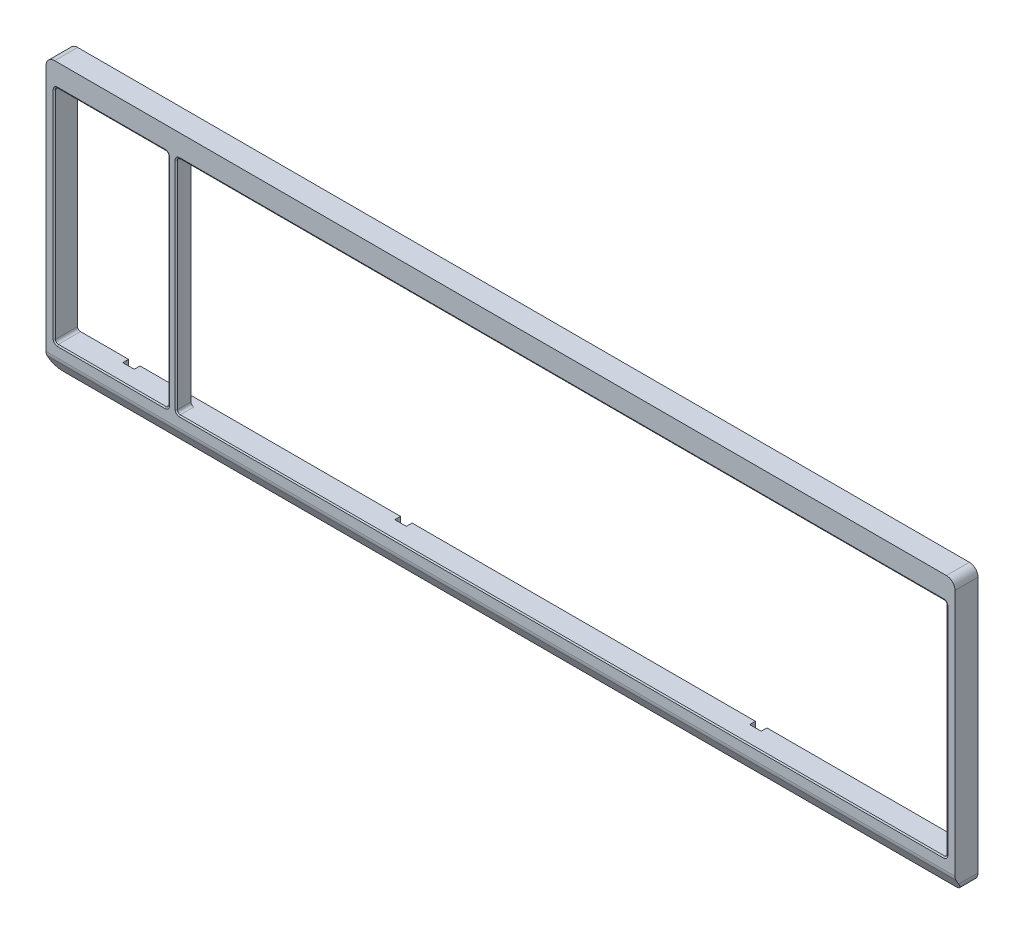
SolidWorks part; units mm, degrees
note: The reader was unsure of these and kept them because the rebuilt part matched: shared geometry of "Sketch3<3>".
ref_plane "Front Plane" through (0, 0, 0) normal (0, 0, 1) x (1, 0, 0)
ref_plane "Top Plane" through (0, 0, 0) normal (0, 1, 0) x (1, 0, 0)
ref_plane "Right Plane" through (0, 0, 0) normal (1, 0, 0) x (0, 0, -1)
sketch "Model" plane through (0, 0, 0) normal (0, 0, 1) x (1, 0, 0)
  line L0 (3.025, -2.525) -> (16.025, -2.525)
  line L1 (3.025, -16.525) -> (16.025, -16.525)
  line L2 (2.525, -3.025) -> (2.525, -16.025)
  line L3 (16.525, -3.025) -> (16.525, -16.025)
  line L4 (22.075, -2.525) -> (35.075, -2.525)
  line L5 (22.075, -16.525) -> (35.075, -16.525)
  line L6 (21.575, -3.025) -> (21.575, -16.025)
  line L7 (35.575, -3.025) -> (35.575, -16.025)
  line L8 (45.8875, -2.525) -> (58.8875, -2.525)
  line L9 (45.8875, -16.525) -> (58.8875, -16.525)
  line L10 (45.3875, -3.025) -> (45.3875, -16.025)
  line L11 (59.3875, -3.025) -> (59.3875, -16.025)
  line L12 (64.9375, -2.525) -> (77.9375, -2.525)
  line L13 (64.9375, -16.525) -> (77.9375, -16.525)
  line L14 (64.4375, -3.025) -> (64.4375, -16.025)
  line L15 (78.4375, -3.025) -> (78.4375, -16.025)
  line L16 (83.9875, -2.525) -> (96.9875, -2.525)
  line L17 (83.9875, -16.525) -> (96.9875, -16.525)
  line L18 (83.4875, -3.025) -> (83.4875, -16.025)
  line L19 (97.4875, -3.025) -> (97.4875, -16.025)
  line L20 (103.0375, -2.525) -> (116.0375, -2.525)
  line L21 (103.0375, -16.525) -> (116.0375, -16.525)
  line L22 (102.5375, -3.025) -> (102.5375, -16.025)
  line L23 (116.5375, -3.025) -> (116.5375, -16.025)
  line L24 (122.0875, -2.525) -> (135.0875, -2.525)
  line L25 (122.0875, -16.525) -> (135.0875, -16.525)
  line L26 (121.5875, -3.025) -> (121.5875, -16.025)
  line L27 (135.5875, -3.025) -> (135.5875, -16.025)
  line L28 (141.1375, -2.525) -> (154.1375, -2.525)
  line L29 (141.1375, -16.525) -> (154.1375, -16.525)
  line L30 (140.6375, -3.025) -> (140.6375, -16.025)
  line L31 (154.6375, -3.025) -> (154.6375, -16.025)
  line L32 (160.1875, -2.525) -> (173.1875, -2.525)
  line L33 (160.1875, -16.525) -> (173.1875, -16.525)
  line L34 (159.6875, -3.025) -> (159.6875, -16.025)
  line L35 (173.6875, -3.025) -> (173.6875, -16.025)
  line L36 (179.2375, -2.525) -> (192.2375, -2.525)
  line L37 (179.2375, -16.525) -> (192.2375, -16.525)
  line L38 (178.7375, -3.025) -> (178.7375, -16.025)
  line L39 (192.7375, -3.025) -> (192.7375, -16.025)
  line L40 (198.2875, -2.525) -> (211.2875, -2.525)
  line L41 (198.2875, -16.525) -> (211.2875, -16.525)
  line L42 (197.7875, -3.025) -> (197.7875, -16.025)
  line L43 (211.7875, -3.025) -> (211.7875, -16.025)
  line L44 (217.3375, -2.525) -> (230.3375, -2.525)
  line L45 (217.3375, -16.525) -> (230.3375, -16.525)
  line L46 (216.8375, -3.025) -> (216.8375, -16.025)
  line L47 (230.8375, -3.025) -> (230.8375, -16.025)
  line L48 (236.3875, -2.525) -> (249.3875, -2.525)
  line L49 (236.3875, -16.525) -> (249.3875, -16.525)
  line L50 (235.8875, -3.025) -> (235.8875, -16.025)
  line L51 (249.8875, -3.025) -> (249.8875, -16.025)
  line L52 (255.4375, -2.525) -> (268.4375, -2.525)
  line L53 (255.4375, -16.525) -> (268.4375, -16.525)
  line L54 (254.9375, -3.025) -> (254.9375, -16.025)
  line L55 (268.9375, -3.025) -> (268.9375, -16.025)
  line L56 (274.4875, -2.525) -> (287.4875, -2.525)
  line L57 (274.4875, -16.525) -> (287.4875, -16.525)
  line L58 (273.9875, -3.025) -> (273.9875, -16.025)
  line L59 (287.9875, -3.025) -> (287.9875, -16.025)
  line L60 (293.5375, -2.525) -> (306.5375, -2.525)
  line L61 (293.5375, -16.525) -> (306.5375, -16.525)
  line L62 (293.0375, -3.025) -> (293.0375, -16.025)
  line L63 (307.0375, -3.025) -> (307.0375, -16.025)
  line L64 (3.025, -21.575) -> (16.025, -21.575)
  line L65 (3.025, -35.575) -> (16.025, -35.575)
  line L66 (2.525, -22.075) -> (2.525, -35.075)
  line L67 (16.525, -22.075) -> (16.525, -35.075)
  line L68 (22.075, -21.575) -> (35.075, -21.575)
  line L69 (22.075, -35.575) -> (35.075, -35.575)
  line L70 (21.575, -22.075) -> (21.575, -35.075)
  line L71 (35.575, -22.075) -> (35.575, -35.075)
  line L72 (48.2687, -21.575) -> (61.2687, -21.575)
  line L73 (48.2687, -35.575) -> (61.2687, -35.575)
  line L74 (47.7687, -22.075) -> (47.7687, -35.075)
  line L75 (61.7687, -22.075) -> (61.7687, -35.075)
  line L76 (69.7, -21.575) -> (82.7, -21.575)
  line L77 (69.7, -35.575) -> (82.7, -35.575)
  line L78 (69.2, -22.075) -> (69.2, -35.075)
  line L79 (83.2, -22.075) -> (83.2, -35.075)
  line L80 (88.75, -21.575) -> (101.75, -21.575)
  line L81 (88.75, -35.575) -> (101.75, -35.575)
  line L82 (88.25, -22.075) -> (88.25, -35.075)
  line L83 (102.25, -22.075) -> (102.25, -35.075)
  line L84 (107.8, -21.575) -> (120.8, -21.575)
  line L85 (107.8, -35.575) -> (120.8, -35.575)
  line L86 (107.3, -22.075) -> (107.3, -35.075)
  line L87 (121.3, -22.075) -> (121.3, -35.075)
  line L88 (126.85, -21.575) -> (139.85, -21.575)
  line L89 (126.85, -35.575) -> (139.85, -35.575)
  line L90 (126.35, -22.075) -> (126.35, -35.075)
  line L91 (140.35, -22.075) -> (140.35, -35.075)
  line L92 (145.9, -21.575) -> (158.9, -21.575)
  line L93 (145.9, -35.575) -> (158.9, -35.575)
  line L94 (145.4, -22.075) -> (145.4, -35.075)
  line L95 (159.4, -22.075) -> (159.4, -35.075)
  line L96 (164.95, -21.575) -> (177.95, -21.575)
  line L97 (164.95, -35.575) -> (177.95, -35.575)
  line L98 (164.45, -22.075) -> (164.45, -35.075)
  line L99 (178.45, -22.075) -> (178.45, -35.075)
  line L100 (184, -21.575) -> (197, -21.575)
  line L101 (184, -35.575) -> (197, -35.575)
  line L102 (183.5, -22.075) -> (183.5, -35.075)
  line L103 (197.5, -22.075) -> (197.5, -35.075)
  line L104 (203.05, -21.575) -> (216.05, -21.575)
  line L105 (203.05, -35.575) -> (216.05, -35.575)
  line L106 (202.55, -22.075) -> (202.55, -35.075)
  line L107 (216.55, -22.075) -> (216.55, -35.075)
  line L108 (222.1, -21.575) -> (235.1, -21.575)
  line L109 (222.1, -35.575) -> (235.1, -35.575)
  line L110 (221.6, -22.075) -> (221.6, -35.075)
  line L111 (235.6, -22.075) -> (235.6, -35.075)
  line L112 (241.15, -21.575) -> (254.15, -21.575)
  line L113 (241.15, -35.575) -> (254.15, -35.575)
  line L114 (240.65, -22.075) -> (240.65, -35.075)
  line L115 (254.65, -22.075) -> (254.65, -35.075)
  line L116 (260.2, -21.575) -> (273.2, -21.575)
  line L117 (260.2, -35.575) -> (273.2, -35.575)
  line L118 (259.7, -22.075) -> (259.7, -35.075)
  line L119 (273.7, -22.075) -> (273.7, -35.075)
  line L120 (286.3938, -21.575) -> (299.3938, -21.575)
  line L121 (286.3938, -35.575) -> (299.3938, -35.575)
  line L122 (285.8938, -22.075) -> (285.8938, -35.075)
  line L123 (299.8938, -22.075) -> (299.8938, -35.075)
  line L124 (281.8938, -21.575) -> (282.3938, -21.575)
  line L125 (281.8938, -35.575) -> (282.3938, -35.575)
  line L126 (281.3938, -22.075) -> (281.3938, -35.075)
  line L127 (282.8938, -22.075) -> (282.8938, -35.075)
  line L128 (303.3938, -21.575) -> (303.8938, -21.575)
  line L129 (303.3938, -35.575) -> (303.8938, -35.575)
  line L130 (302.8938, -22.075) -> (302.8938, -35.075)
  line L131 (304.3938, -22.075) -> (304.3938, -35.075)
  line L132 (3.025, -40.625) -> (16.025, -40.625)
  line L133 (3.025, -54.625) -> (16.025, -54.625)
  line L134 (2.525, -41.125) -> (2.525, -54.125)
  line L135 (16.525, -41.125) -> (16.525, -54.125)
  line L136 (22.075, -40.625) -> (35.075, -40.625)
  line L137 (22.075, -54.625) -> (35.075, -54.625)
  line L138 (21.575, -41.125) -> (21.575, -54.125)
  line L139 (35.575, -41.125) -> (35.575, -54.125)
  line L140 (53.0312, -40.625) -> (66.0312, -40.625)
  line L141 (53.0312, -54.625) -> (66.0312, -54.625)
  line L142 (52.5312, -41.125) -> (52.5312, -54.125)
  line L143 (66.5312, -41.125) -> (66.5312, -54.125)
  line L144 (48.5312, -40.625) -> (49.0312, -40.625)
  line L145 (48.5312, -54.625) -> (49.0312, -54.625)
  line L146 (48.0312, -41.125) -> (48.0312, -54.125)
  line L147 (49.5312, -41.125) -> (49.5312, -54.125)
  line L148 (70.0312, -40.625) -> (70.5312, -40.625)
  line L149 (70.0312, -54.625) -> (70.5312, -54.625)
  line L150 (69.5312, -41.125) -> (69.5312, -54.125)
  line L151 (71.0312, -41.125) -> (71.0312, -54.125)
  line L152 (79.225, -40.625) -> (92.225, -40.625)
  line L153 (79.225, -54.625) -> (92.225, -54.625)
  line L154 (78.725, -41.125) -> (78.725, -54.125)
  line L155 (92.725, -41.125) -> (92.725, -54.125)
  line L156 (98.275, -40.625) -> (111.275, -40.625)
  line L157 (98.275, -54.625) -> (111.275, -54.625)
  line L158 (97.775, -41.125) -> (97.775, -54.125)
  line L159 (111.775, -41.125) -> (111.775, -54.125)
  line L160 (117.325, -40.625) -> (130.325, -40.625)
  line L161 (117.325, -54.625) -> (130.325, -54.625)
  line L162 (116.825, -41.125) -> (116.825, -54.125)
  line L163 (130.825, -41.125) -> (130.825, -54.125)
  line L164 (136.375, -40.625) -> (149.375, -40.625)
  line L165 (136.375, -54.625) -> (149.375, -54.625)
  line L166 (135.875, -41.125) -> (135.875, -54.125)
  line L167 (149.875, -41.125) -> (149.875, -54.125)
  line L168 (155.425, -40.625) -> (168.425, -40.625)
  line L169 (155.425, -54.625) -> (168.425, -54.625)
  line L170 (154.925, -41.125) -> (154.925, -54.125)
  line L171 (168.925, -41.125) -> (168.925, -54.125)
  line L172 (174.475, -40.625) -> (187.475, -40.625)
  line L173 (174.475, -54.625) -> (187.475, -54.625)
  line L174 (173.975, -41.125) -> (173.975, -54.125)
  line L175 (187.975, -41.125) -> (187.975, -54.125)
  line L176 (193.525, -40.625) -> (206.525, -40.625)
  line L177 (193.525, -54.625) -> (206.525, -54.625)
  line L178 (193.025, -41.125) -> (193.025, -54.125)
  line L179 (207.025, -41.125) -> (207.025, -54.125)
  line L180 (212.575, -40.625) -> (225.575, -40.625)
  line L181 (212.575, -54.625) -> (225.575, -54.625)
  line L182 (212.075, -41.125) -> (212.075, -54.125)
  line L183 (226.075, -41.125) -> (226.075, -54.125)
  line L184 (231.625, -40.625) -> (244.625, -40.625)
  line L185 (231.625, -54.625) -> (244.625, -54.625)
  line L186 (231.125, -41.125) -> (231.125, -54.125)
  line L187 (245.125, -41.125) -> (245.125, -54.125)
  line L188 (250.675, -40.625) -> (263.675, -40.625)
  line L189 (250.675, -54.625) -> (263.675, -54.625)
  line L190 (250.175, -41.125) -> (250.175, -54.125)
  line L191 (264.175, -41.125) -> (264.175, -54.125)
  line L192 (269.725, -40.625) -> (282.725, -40.625)
  line L193 (269.725, -54.625) -> (282.725, -54.625)
  line L194 (269.225, -41.125) -> (269.225, -54.125)
  line L195 (283.225, -41.125) -> (283.225, -54.125)
  line L196 (291.1562, -40.625) -> (304.1562, -40.625)
  line L197 (291.1562, -54.625) -> (304.1562, -54.625)
  line L198 (290.6562, -41.125) -> (290.6562, -54.125)
  line L199 (304.6562, -41.125) -> (304.6562, -54.125)
  line L200 (3.025, -59.675) -> (16.025, -59.675)
  line L201 (3.025, -73.675) -> (16.025, -73.675)
  line L202 (2.525, -60.175) -> (2.525, -73.175)
  line L203 (16.525, -60.175) -> (16.525, -73.175)
  line L204 (22.075, -59.675) -> (35.075, -59.675)
  line L205 (22.075, -73.675) -> (35.075, -73.675)
  line L206 (21.575, -60.175) -> (21.575, -73.175)
  line L207 (35.575, -60.175) -> (35.575, -73.175)
  line L208 (48.2687, -59.675) -> (61.2687, -59.675)
  line L209 (48.2687, -73.675) -> (61.2687, -73.675)
  line L210 (47.7687, -60.175) -> (47.7687, -73.175)
  line L211 (61.7687, -60.175) -> (61.7687, -73.175)
  line L212 (69.7, -59.675) -> (82.7, -59.675)
  line L213 (69.7, -73.675) -> (82.7, -73.675)
  line L214 (69.2, -60.175) -> (69.2, -73.175)
  line L215 (83.2, -60.175) -> (83.2, -73.175)
  line L216 (93.5125, -59.675) -> (106.5125, -59.675)
  line L217 (93.5125, -73.675) -> (106.5125, -73.675)
  line L218 (93.0125, -60.175) -> (93.0125, -73.175)
  line L219 (107.0125, -60.175) -> (107.0125, -73.175)
  line L220 (89.0125, -59.675) -> (89.5125, -59.675)
  line L221 (89.0125, -73.675) -> (89.5125, -73.675)
  line L222 (88.5125, -60.175) -> (88.5125, -73.175)
  line L223 (90.0125, -60.175) -> (90.0125, -73.175)
  line L224 (110.5125, -59.675) -> (111.0125, -59.675)
  line L225 (110.5125, -73.675) -> (111.0125, -73.675)
  line L226 (110.0125, -60.175) -> (110.0125, -73.175)
  line L227 (111.5125, -60.175) -> (111.5125, -73.175)
  line L228 (167.3313, -59.675) -> (180.3313, -59.675)
  line L229 (167.3313, -73.675) -> (180.3313, -73.675)
  line L230 (166.8313, -60.175) -> (166.8313, -73.175)
  line L231 (180.8313, -60.175) -> (180.8313, -73.175)
  line L232 (120.8312, -60.675) -> (126.8313, -60.675)
  line L233 (120.8312, -75.675) -> (126.8313, -75.675)
  line L234 (120.3312, -61.175) -> (120.3312, -75.175)
  line L235 (127.3313, -61.175) -> (127.3313, -75.175)
  line L236 (220.8313, -60.675) -> (226.8313, -60.675)
  line L237 (220.8313, -75.675) -> (226.8313, -75.675)
  line L238 (220.3313, -61.175) -> (220.3313, -75.175)
  line L239 (227.3313, -61.175) -> (227.3313, -75.175)
  line L240 (241.15, -59.675) -> (254.15, -59.675)
  line L241 (241.15, -73.675) -> (254.15, -73.675)
  line L242 (240.65, -60.175) -> (240.65, -73.175)
  line L243 (254.65, -60.175) -> (254.65, -73.175)
  line L244 (236.65, -59.675) -> (237.15, -59.675)
  line L245 (236.65, -73.675) -> (237.15, -73.675)
  line L246 (236.15, -60.175) -> (236.15, -73.175)
  line L247 (237.65, -60.175) -> (237.65, -73.175)
  line L248 (258.15, -59.675) -> (258.65, -59.675)
  line L249 (258.15, -73.675) -> (258.65, -73.675)
  line L250 (257.65, -60.175) -> (257.65, -73.175)
  line L251 (259.15, -60.175) -> (259.15, -73.175)
  line L252 (264.9625, -59.675) -> (277.9625, -59.675)
  line L253 (264.9625, -73.675) -> (277.9625, -73.675)
  line L254 (264.4625, -60.175) -> (264.4625, -73.175)
  line L255 (278.4625, -60.175) -> (278.4625, -73.175)
  line L256 (288.775, -59.675) -> (301.775, -59.675)
  line L257 (288.775, -73.675) -> (301.775, -73.675)
  line L258 (288.275, -60.175) -> (288.275, -73.175)
  line L259 (302.275, -60.175) -> (302.275, -73.175)
  line L260 (284.275, -59.675) -> (284.775, -59.675)
  line L261 (284.275, -73.675) -> (284.775, -73.675)
  line L262 (283.775, -60.175) -> (283.775, -73.175)
  line L263 (285.275, -60.175) -> (285.275, -73.175)
  line L264 (305.775, -59.675) -> (306.275, -59.675)
  line L265 (305.775, -73.675) -> (306.275, -73.675)
  line L266 (305.275, -60.175) -> (305.275, -73.175)
  line L267 (306.775, -60.175) -> (306.775, -73.175)
  line L268 (0, -76.2) -> (309.5625, -76.2)
  line L269 (0, 0) -> (309.5625, 0)
  line L270 (0, -76.2) -> (0, 0)
  line L271 (309.5625, -76.2) -> (309.5625, 0)
  arc A0 (3.025, -2.525) -> (2.525, -3.025) centre (3.025, -3.025) ccw
  arc A1 (16.525, -3.025) -> (16.025, -2.525) centre (16.025, -3.025) ccw
  arc A2 (2.525, -16.025) -> (3.025, -16.525) centre (3.025, -16.025) ccw
  arc A3 (16.025, -16.525) -> (16.525, -16.025) centre (16.025, -16.025) ccw
  arc A4 (22.075, -2.525) -> (21.575, -3.025) centre (22.075, -3.025) ccw
  arc A5 (35.575, -3.025) -> (35.075, -2.525) centre (35.075, -3.025) ccw
  arc A6 (21.575, -16.025) -> (22.075, -16.525) centre (22.075, -16.025) ccw
  arc A7 (35.075, -16.525) -> (35.575, -16.025) centre (35.075, -16.025) ccw
  arc A8 (45.8875, -2.525) -> (45.3875, -3.025) centre (45.8875, -3.025) ccw
  arc A9 (59.3875, -3.025) -> (58.8875, -2.525) centre (58.8875, -3.025) ccw
  arc A10 (45.3875, -16.025) -> (45.8875, -16.525) centre (45.8875, -16.025) ccw
  arc A11 (58.8875, -16.525) -> (59.3875, -16.025) centre (58.8875, -16.025) ccw
  arc A12 (64.9375, -2.525) -> (64.4375, -3.025) centre (64.9375, -3.025) ccw
  arc A13 (78.4375, -3.025) -> (77.9375, -2.525) centre (77.9375, -3.025) ccw
  arc A14 (64.4375, -16.025) -> (64.9375, -16.525) centre (64.9375, -16.025) ccw
  arc A15 (77.9375, -16.525) -> (78.4375, -16.025) centre (77.9375, -16.025) ccw
  arc A16 (83.9875, -2.525) -> (83.4875, -3.025) centre (83.9875, -3.025) ccw
  arc A17 (97.4875, -3.025) -> (96.9875, -2.525) centre (96.9875, -3.025) ccw
  arc A18 (83.4875, -16.025) -> (83.9875, -16.525) centre (83.9875, -16.025) ccw
  arc A19 (96.9875, -16.525) -> (97.4875, -16.025) centre (96.9875, -16.025) ccw
  arc A20 (103.0375, -2.525) -> (102.5375, -3.025) centre (103.0375, -3.025) ccw
  arc A21 (116.5375, -3.025) -> (116.0375, -2.525) centre (116.0375, -3.025) ccw
  arc A22 (102.5375, -16.025) -> (103.0375, -16.525) centre (103.0375, -16.025) ccw
  arc A23 (116.0375, -16.525) -> (116.5375, -16.025) centre (116.0375, -16.025) ccw
  arc A24 (122.0875, -2.525) -> (121.5875, -3.025) centre (122.0875, -3.025) ccw
  arc A25 (135.5875, -3.025) -> (135.0875, -2.525) centre (135.0875, -3.025) ccw
  arc A26 (121.5875, -16.025) -> (122.0875, -16.525) centre (122.0875, -16.025) ccw
  arc A27 (135.0875, -16.525) -> (135.5875, -16.025) centre (135.0875, -16.025) ccw
  arc A28 (141.1375, -2.525) -> (140.6375, -3.025) centre (141.1375, -3.025) ccw
  arc A29 (154.6375, -3.025) -> (154.1375, -2.525) centre (154.1375, -3.025) ccw
  arc A30 (140.6375, -16.025) -> (141.1375, -16.525) centre (141.1375, -16.025) ccw
  arc A31 (154.1375, -16.525) -> (154.6375, -16.025) centre (154.1375, -16.025) ccw
  arc A32 (160.1875, -2.525) -> (159.6875, -3.025) centre (160.1875, -3.025) ccw
  arc A33 (173.6875, -3.025) -> (173.1875, -2.525) centre (173.1875, -3.025) ccw
  arc A34 (159.6875, -16.025) -> (160.1875, -16.525) centre (160.1875, -16.025) ccw
  arc A35 (173.1875, -16.525) -> (173.6875, -16.025) centre (173.1875, -16.025) ccw
  arc A36 (179.2375, -2.525) -> (178.7375, -3.025) centre (179.2375, -3.025) ccw
  arc A37 (192.7375, -3.025) -> (192.2375, -2.525) centre (192.2375, -3.025) ccw
  arc A38 (178.7375, -16.025) -> (179.2375, -16.525) centre (179.2375, -16.025) ccw
  arc A39 (192.2375, -16.525) -> (192.7375, -16.025) centre (192.2375, -16.025) ccw
  arc A40 (198.2875, -2.525) -> (197.7875, -3.025) centre (198.2875, -3.025) ccw
  arc A41 (211.7875, -3.025) -> (211.2875, -2.525) centre (211.2875, -3.025) ccw
  arc A42 (197.7875, -16.025) -> (198.2875, -16.525) centre (198.2875, -16.025) ccw
  arc A43 (211.2875, -16.525) -> (211.7875, -16.025) centre (211.2875, -16.025) ccw
  arc A44 (217.3375, -2.525) -> (216.8375, -3.025) centre (217.3375, -3.025) ccw
  arc A45 (230.8375, -3.025) -> (230.3375, -2.525) centre (230.3375, -3.025) ccw
  arc A46 (216.8375, -16.025) -> (217.3375, -16.525) centre (217.3375, -16.025) ccw
  arc A47 (230.3375, -16.525) -> (230.8375, -16.025) centre (230.3375, -16.025) ccw
  arc A48 (236.3875, -2.525) -> (235.8875, -3.025) centre (236.3875, -3.025) ccw
  arc A49 (249.8875, -3.025) -> (249.3875, -2.525) centre (249.3875, -3.025) ccw
  arc A50 (235.8875, -16.025) -> (236.3875, -16.525) centre (236.3875, -16.025) ccw
  arc A51 (249.3875, -16.525) -> (249.8875, -16.025) centre (249.3875, -16.025) ccw
  arc A52 (255.4375, -2.525) -> (254.9375, -3.025) centre (255.4375, -3.025) ccw
  arc A53 (268.9375, -3.025) -> (268.4375, -2.525) centre (268.4375, -3.025) ccw
  arc A54 (254.9375, -16.025) -> (255.4375, -16.525) centre (255.4375, -16.025) ccw
  arc A55 (268.4375, -16.525) -> (268.9375, -16.025) centre (268.4375, -16.025) ccw
  arc A56 (274.4875, -2.525) -> (273.9875, -3.025) centre (274.4875, -3.025) ccw
  arc A57 (287.9875, -3.025) -> (287.4875, -2.525) centre (287.4875, -3.025) ccw
  arc A58 (273.9875, -16.025) -> (274.4875, -16.525) centre (274.4875, -16.025) ccw
  arc A59 (287.4875, -16.525) -> (287.9875, -16.025) centre (287.4875, -16.025) ccw
  arc A60 (293.5375, -2.525) -> (293.0375, -3.025) centre (293.5375, -3.025) ccw
  arc A61 (307.0375, -3.025) -> (306.5375, -2.525) centre (306.5375, -3.025) ccw
  arc A62 (293.0375, -16.025) -> (293.5375, -16.525) centre (293.5375, -16.025) ccw
  arc A63 (306.5375, -16.525) -> (307.0375, -16.025) centre (306.5375, -16.025) ccw
  arc A64 (3.025, -21.575) -> (2.525, -22.075) centre (3.025, -22.075) ccw
  arc A65 (16.525, -22.075) -> (16.025, -21.575) centre (16.025, -22.075) ccw
  arc A66 (2.525, -35.075) -> (3.025, -35.575) centre (3.025, -35.075) ccw
  arc A67 (16.025, -35.575) -> (16.525, -35.075) centre (16.025, -35.075) ccw
  arc A68 (22.075, -21.575) -> (21.575, -22.075) centre (22.075, -22.075) ccw
  arc A69 (35.575, -22.075) -> (35.075, -21.575) centre (35.075, -22.075) ccw
  arc A70 (21.575, -35.075) -> (22.075, -35.575) centre (22.075, -35.075) ccw
  arc A71 (35.075, -35.575) -> (35.575, -35.075) centre (35.075, -35.075) ccw
  arc A72 (48.2687, -21.575) -> (47.7687, -22.075) centre (48.2687, -22.075) ccw
  arc A73 (61.7687, -22.075) -> (61.2687, -21.575) centre (61.2687, -22.075) ccw
  arc A74 (47.7687, -35.075) -> (48.2687, -35.575) centre (48.2687, -35.075) ccw
  arc A75 (61.2687, -35.575) -> (61.7687, -35.075) centre (61.2687, -35.075) ccw
  arc A76 (69.7, -21.575) -> (69.2, -22.075) centre (69.7, -22.075) ccw
  arc A77 (83.2, -22.075) -> (82.7, -21.575) centre (82.7, -22.075) ccw
  arc A78 (69.2, -35.075) -> (69.7, -35.575) centre (69.7, -35.075) ccw
  arc A79 (82.7, -35.575) -> (83.2, -35.075) centre (82.7, -35.075) ccw
  arc A80 (88.75, -21.575) -> (88.25, -22.075) centre (88.75, -22.075) ccw
  arc A81 (102.25, -22.075) -> (101.75, -21.575) centre (101.75, -22.075) ccw
  arc A82 (88.25, -35.075) -> (88.75, -35.575) centre (88.75, -35.075) ccw
  arc A83 (101.75, -35.575) -> (102.25, -35.075) centre (101.75, -35.075) ccw
  arc A84 (107.8, -21.575) -> (107.3, -22.075) centre (107.8, -22.075) ccw
  arc A85 (121.3, -22.075) -> (120.8, -21.575) centre (120.8, -22.075) ccw
  arc A86 (107.3, -35.075) -> (107.8, -35.575) centre (107.8, -35.075) ccw
  arc A87 (120.8, -35.575) -> (121.3, -35.075) centre (120.8, -35.075) ccw
  arc A88 (126.85, -21.575) -> (126.35, -22.075) centre (126.85, -22.075) ccw
  arc A89 (140.35, -22.075) -> (139.85, -21.575) centre (139.85, -22.075) ccw
  arc A90 (126.35, -35.075) -> (126.85, -35.575) centre (126.85, -35.075) ccw
  arc A91 (139.85, -35.575) -> (140.35, -35.075) centre (139.85, -35.075) ccw
  arc A92 (145.9, -21.575) -> (145.4, -22.075) centre (145.9, -22.075) ccw
  arc A93 (159.4, -22.075) -> (158.9, -21.575) centre (158.9, -22.075) ccw
  arc A94 (145.4, -35.075) -> (145.9, -35.575) centre (145.9, -35.075) ccw
  arc A95 (158.9, -35.575) -> (159.4, -35.075) centre (158.9, -35.075) ccw
  arc A96 (164.95, -21.575) -> (164.45, -22.075) centre (164.95, -22.075) ccw
  arc A97 (178.45, -22.075) -> (177.95, -21.575) centre (177.95, -22.075) ccw
  arc A98 (164.45, -35.075) -> (164.95, -35.575) centre (164.95, -35.075) ccw
  arc A99 (177.95, -35.575) -> (178.45, -35.075) centre (177.95, -35.075) ccw
  arc A100 (184, -21.575) -> (183.5, -22.075) centre (184, -22.075) ccw
  arc A101 (197.5, -22.075) -> (197, -21.575) centre (197, -22.075) ccw
  arc A102 (183.5, -35.075) -> (184, -35.575) centre (184, -35.075) ccw
  arc A103 (197, -35.575) -> (197.5, -35.075) centre (197, -35.075) ccw
  arc A104 (203.05, -21.575) -> (202.55, -22.075) centre (203.05, -22.075) ccw
  arc A105 (216.55, -22.075) -> (216.05, -21.575) centre (216.05, -22.075) ccw
  arc A106 (202.55, -35.075) -> (203.05, -35.575) centre (203.05, -35.075) ccw
  arc A107 (216.05, -35.575) -> (216.55, -35.075) centre (216.05, -35.075) ccw
  arc A108 (222.1, -21.575) -> (221.6, -22.075) centre (222.1, -22.075) ccw
  arc A109 (235.6, -22.075) -> (235.1, -21.575) centre (235.1, -22.075) ccw
  arc A110 (221.6, -35.075) -> (222.1, -35.575) centre (222.1, -35.075) ccw
  arc A111 (235.1, -35.575) -> (235.6, -35.075) centre (235.1, -35.075) ccw
  arc A112 (241.15, -21.575) -> (240.65, -22.075) centre (241.15, -22.075) ccw
  arc A113 (254.65, -22.075) -> (254.15, -21.575) centre (254.15, -22.075) ccw
  arc A114 (240.65, -35.075) -> (241.15, -35.575) centre (241.15, -35.075) ccw
  arc A115 (254.15, -35.575) -> (254.65, -35.075) centre (254.15, -35.075) ccw
  arc A116 (260.2, -21.575) -> (259.7, -22.075) centre (260.2, -22.075) ccw
  arc A117 (273.7, -22.075) -> (273.2, -21.575) centre (273.2, -22.075) ccw
  arc A118 (259.7, -35.075) -> (260.2, -35.575) centre (260.2, -35.075) ccw
  arc A119 (273.2, -35.575) -> (273.7, -35.075) centre (273.2, -35.075) ccw
  arc A120 (286.3938, -21.575) -> (285.8938, -22.075) centre (286.3938, -22.075) ccw
  arc A121 (299.8938, -22.075) -> (299.3938, -21.575) centre (299.3938, -22.075) ccw
  arc A122 (285.8938, -35.075) -> (286.3938, -35.575) centre (286.3938, -35.075) ccw
  arc A123 (299.3938, -35.575) -> (299.8938, -35.075) centre (299.3938, -35.075) ccw
  arc A124 (281.8938, -21.575) -> (281.3938, -22.075) centre (281.8938, -22.075) ccw
  arc A125 (282.8938, -22.075) -> (282.3938, -21.575) centre (282.3938, -22.075) ccw
  arc A126 (281.3938, -35.075) -> (281.8938, -35.575) centre (281.8938, -35.075) ccw
  arc A127 (282.3938, -35.575) -> (282.8938, -35.075) centre (282.3938, -35.075) ccw
  arc A128 (303.3938, -21.575) -> (302.8938, -22.075) centre (303.3938, -22.075) ccw
  arc A129 (304.3938, -22.075) -> (303.8938, -21.575) centre (303.8938, -22.075) ccw
  arc A130 (302.8938, -35.075) -> (303.3938, -35.575) centre (303.3938, -35.075) ccw
  arc A131 (303.8938, -35.575) -> (304.3938, -35.075) centre (303.8938, -35.075) ccw
  arc A132 (3.025, -40.625) -> (2.525, -41.125) centre (3.025, -41.125) ccw
  arc A133 (16.525, -41.125) -> (16.025, -40.625) centre (16.025, -41.125) ccw
  arc A134 (2.525, -54.125) -> (3.025, -54.625) centre (3.025, -54.125) ccw
  arc A135 (16.025, -54.625) -> (16.525, -54.125) centre (16.025, -54.125) ccw
  arc A136 (22.075, -40.625) -> (21.575, -41.125) centre (22.075, -41.125) ccw
  arc A137 (35.575, -41.125) -> (35.075, -40.625) centre (35.075, -41.125) ccw
  arc A138 (21.575, -54.125) -> (22.075, -54.625) centre (22.075, -54.125) ccw
  arc A139 (35.075, -54.625) -> (35.575, -54.125) centre (35.075, -54.125) ccw
  arc A140 (53.0312, -40.625) -> (52.5312, -41.125) centre (53.0312, -41.125) ccw
  arc A141 (66.5312, -41.125) -> (66.0312, -40.625) centre (66.0312, -41.125) ccw
  arc A142 (52.5312, -54.125) -> (53.0312, -54.625) centre (53.0312, -54.125) ccw
  arc A143 (66.0312, -54.625) -> (66.5312, -54.125) centre (66.0312, -54.125) ccw
  arc A144 (48.5312, -40.625) -> (48.0312, -41.125) centre (48.5312, -41.125) ccw
  arc A145 (49.5312, -41.125) -> (49.0312, -40.625) centre (49.0312, -41.125) ccw
  arc A146 (48.0312, -54.125) -> (48.5312, -54.625) centre (48.5312, -54.125) ccw
  arc A147 (49.0312, -54.625) -> (49.5312, -54.125) centre (49.0312, -54.125) ccw
  arc A148 (70.0312, -40.625) -> (69.5312, -41.125) centre (70.0312, -41.125) ccw
  arc A149 (71.0312, -41.125) -> (70.5312, -40.625) centre (70.5312, -41.125) ccw
  arc A150 (69.5312, -54.125) -> (70.0312, -54.625) centre (70.0312, -54.125) ccw
  arc A151 (70.5312, -54.625) -> (71.0312, -54.125) centre (70.5312, -54.125) ccw
  arc A152 (79.225, -40.625) -> (78.725, -41.125) centre (79.225, -41.125) ccw
  arc A153 (92.725, -41.125) -> (92.225, -40.625) centre (92.225, -41.125) ccw
  arc A154 (78.725, -54.125) -> (79.225, -54.625) centre (79.225, -54.125) ccw
  arc A155 (92.225, -54.625) -> (92.725, -54.125) centre (92.225, -54.125) ccw
  arc A156 (98.275, -40.625) -> (97.775, -41.125) centre (98.275, -41.125) ccw
  arc A157 (111.775, -41.125) -> (111.275, -40.625) centre (111.275, -41.125) ccw
  arc A158 (97.775, -54.125) -> (98.275, -54.625) centre (98.275, -54.125) ccw
  arc A159 (111.275, -54.625) -> (111.775, -54.125) centre (111.275, -54.125) ccw
  arc A160 (117.325, -40.625) -> (116.825, -41.125) centre (117.325, -41.125) ccw
  arc A161 (130.825, -41.125) -> (130.325, -40.625) centre (130.325, -41.125) ccw
  arc A162 (116.825, -54.125) -> (117.325, -54.625) centre (117.325, -54.125) ccw
  arc A163 (130.325, -54.625) -> (130.825, -54.125) centre (130.325, -54.125) ccw
  arc A164 (136.375, -40.625) -> (135.875, -41.125) centre (136.375, -41.125) ccw
  arc A165 (149.875, -41.125) -> (149.375, -40.625) centre (149.375, -41.125) ccw
  arc A166 (135.875, -54.125) -> (136.375, -54.625) centre (136.375, -54.125) ccw
  arc A167 (149.375, -54.625) -> (149.875, -54.125) centre (149.375, -54.125) ccw
  arc A168 (155.425, -40.625) -> (154.925, -41.125) centre (155.425, -41.125) ccw
  arc A169 (168.925, -41.125) -> (168.425, -40.625) centre (168.425, -41.125) ccw
  arc A170 (154.925, -54.125) -> (155.425, -54.625) centre (155.425, -54.125) ccw
  arc A171 (168.425, -54.625) -> (168.925, -54.125) centre (168.425, -54.125) ccw
  arc A172 (174.475, -40.625) -> (173.975, -41.125) centre (174.475, -41.125) ccw
  arc A173 (187.975, -41.125) -> (187.475, -40.625) centre (187.475, -41.125) ccw
  arc A174 (173.975, -54.125) -> (174.475, -54.625) centre (174.475, -54.125) ccw
  arc A175 (187.475, -54.625) -> (187.975, -54.125) centre (187.475, -54.125) ccw
  arc A176 (193.525, -40.625) -> (193.025, -41.125) centre (193.525, -41.125) ccw
  arc A177 (207.025, -41.125) -> (206.525, -40.625) centre (206.525, -41.125) ccw
  arc A178 (193.025, -54.125) -> (193.525, -54.625) centre (193.525, -54.125) ccw
  arc A179 (206.525, -54.625) -> (207.025, -54.125) centre (206.525, -54.125) ccw
  arc A180 (212.575, -40.625) -> (212.075, -41.125) centre (212.575, -41.125) ccw
  arc A181 (226.075, -41.125) -> (225.575, -40.625) centre (225.575, -41.125) ccw
  arc A182 (212.075, -54.125) -> (212.575, -54.625) centre (212.575, -54.125) ccw
  arc A183 (225.575, -54.625) -> (226.075, -54.125) centre (225.575, -54.125) ccw
  arc A184 (231.625, -40.625) -> (231.125, -41.125) centre (231.625, -41.125) ccw
  arc A185 (245.125, -41.125) -> (244.625, -40.625) centre (244.625, -41.125) ccw
  arc A186 (231.125, -54.125) -> (231.625, -54.625) centre (231.625, -54.125) ccw
  arc A187 (244.625, -54.625) -> (245.125, -54.125) centre (244.625, -54.125) ccw
  arc A188 (250.675, -40.625) -> (250.175, -41.125) centre (250.675, -41.125) ccw
  arc A189 (264.175, -41.125) -> (263.675, -40.625) centre (263.675, -41.125) ccw
  arc A190 (250.175, -54.125) -> (250.675, -54.625) centre (250.675, -54.125) ccw
  arc A191 (263.675, -54.625) -> (264.175, -54.125) centre (263.675, -54.125) ccw
  arc A192 (269.725, -40.625) -> (269.225, -41.125) centre (269.725, -41.125) ccw
  arc A193 (283.225, -41.125) -> (282.725, -40.625) centre (282.725, -41.125) ccw
  arc A194 (269.225, -54.125) -> (269.725, -54.625) centre (269.725, -54.125) ccw
  arc A195 (282.725, -54.625) -> (283.225, -54.125) centre (282.725, -54.125) ccw
  arc A196 (291.1562, -40.625) -> (290.6562, -41.125) centre (291.1562, -41.125) ccw
  arc A197 (304.6562, -41.125) -> (304.1562, -40.625) centre (304.1562, -41.125) ccw
  arc A198 (290.6562, -54.125) -> (291.1562, -54.625) centre (291.1562, -54.125) ccw
  arc A199 (304.1562, -54.625) -> (304.6562, -54.125) centre (304.1562, -54.125) ccw
  arc A200 (3.025, -59.675) -> (2.525, -60.175) centre (3.025, -60.175) ccw
  arc A201 (16.525, -60.175) -> (16.025, -59.675) centre (16.025, -60.175) ccw
  arc A202 (2.525, -73.175) -> (3.025, -73.675) centre (3.025, -73.175) ccw
  arc A203 (16.025, -73.675) -> (16.525, -73.175) centre (16.025, -73.175) ccw
  arc A204 (22.075, -59.675) -> (21.575, -60.175) centre (22.075, -60.175) ccw
  arc A205 (35.575, -60.175) -> (35.075, -59.675) centre (35.075, -60.175) ccw
  arc A206 (21.575, -73.175) -> (22.075, -73.675) centre (22.075, -73.175) ccw
  arc A207 (35.075, -73.675) -> (35.575, -73.175) centre (35.075, -73.175) ccw
  arc A208 (48.2687, -59.675) -> (47.7687, -60.175) centre (48.2687, -60.175) ccw
  arc A209 (61.7687, -60.175) -> (61.2687, -59.675) centre (61.2687, -60.175) ccw
  arc A210 (47.7687, -73.175) -> (48.2687, -73.675) centre (48.2687, -73.175) ccw
  arc A211 (61.2687, -73.675) -> (61.7687, -73.175) centre (61.2687, -73.175) ccw
  arc A212 (69.7, -59.675) -> (69.2, -60.175) centre (69.7, -60.175) ccw
  arc A213 (83.2, -60.175) -> (82.7, -59.675) centre (82.7, -60.175) ccw
  arc A214 (69.2, -73.175) -> (69.7, -73.675) centre (69.7, -73.175) ccw
  arc A215 (82.7, -73.675) -> (83.2, -73.175) centre (82.7, -73.175) ccw
  arc A216 (93.5125, -59.675) -> (93.0125, -60.175) centre (93.5125, -60.175) ccw
  arc A217 (107.0125, -60.175) -> (106.5125, -59.675) centre (106.5125, -60.175) ccw
  arc A218 (93.0125, -73.175) -> (93.5125, -73.675) centre (93.5125, -73.175) ccw
  arc A219 (106.5125, -73.675) -> (107.0125, -73.175) centre (106.5125, -73.175) ccw
  arc A220 (89.0125, -59.675) -> (88.5125, -60.175) centre (89.0125, -60.175) ccw
  arc A221 (90.0125, -60.175) -> (89.5125, -59.675) centre (89.5125, -60.175) ccw
  arc A222 (88.5125, -73.175) -> (89.0125, -73.675) centre (89.0125, -73.175) ccw
  arc A223 (89.5125, -73.675) -> (90.0125, -73.175) centre (89.5125, -73.175) ccw
  arc A224 (110.5125, -59.675) -> (110.0125, -60.175) centre (110.5125, -60.175) ccw
  arc A225 (111.5125, -60.175) -> (111.0125, -59.675) centre (111.0125, -60.175) ccw
  arc A226 (110.0125, -73.175) -> (110.5125, -73.675) centre (110.5125, -73.175) ccw
  arc A227 (111.0125, -73.675) -> (111.5125, -73.175) centre (111.0125, -73.175) ccw
  arc A228 (167.3313, -59.675) -> (166.8313, -60.175) centre (167.3313, -60.175) ccw
  arc A229 (180.8313, -60.175) -> (180.3313, -59.675) centre (180.3313, -60.175) ccw
  arc A230 (166.8313, -73.175) -> (167.3313, -73.675) centre (167.3313, -73.175) ccw
  arc A231 (180.3313, -73.675) -> (180.8313, -73.175) centre (180.3313, -73.175) ccw
  arc A232 (120.8312, -60.675) -> (120.3312, -61.175) centre (120.8312, -61.175) ccw
  arc A233 (127.3313, -61.175) -> (126.8313, -60.675) centre (126.8313, -61.175) ccw
  arc A234 (120.3312, -75.175) -> (120.8312, -75.675) centre (120.8312, -75.175) ccw
  arc A235 (126.8313, -75.675) -> (127.3313, -75.175) centre (126.8313, -75.175) ccw
  arc A236 (220.8313, -60.675) -> (220.3313, -61.175) centre (220.8313, -61.175) ccw
  arc A237 (227.3313, -61.175) -> (226.8313, -60.675) centre (226.8313, -61.175) ccw
  arc A238 (220.3313, -75.175) -> (220.8313, -75.675) centre (220.8313, -75.175) ccw
  arc A239 (226.8313, -75.675) -> (227.3313, -75.175) centre (226.8313, -75.175) ccw
  arc A240 (241.15, -59.675) -> (240.65, -60.175) centre (241.15, -60.175) ccw
  arc A241 (254.65, -60.175) -> (254.15, -59.675) centre (254.15, -60.175) ccw
  arc A242 (240.65, -73.175) -> (241.15, -73.675) centre (241.15, -73.175) ccw
  arc A243 (254.15, -73.675) -> (254.65, -73.175) centre (254.15, -73.175) ccw
  arc A244 (236.65, -59.675) -> (236.15, -60.175) centre (236.65, -60.175) ccw
  arc A245 (237.65, -60.175) -> (237.15, -59.675) centre (237.15, -60.175) ccw
  arc A246 (236.15, -73.175) -> (236.65, -73.675) centre (236.65, -73.175) ccw
  arc A247 (237.15, -73.675) -> (237.65, -73.175) centre (237.15, -73.175) ccw
  arc A248 (258.15, -59.675) -> (257.65, -60.175) centre (258.15, -60.175) ccw
  arc A249 (259.15, -60.175) -> (258.65, -59.675) centre (258.65, -60.175) ccw
  arc A250 (257.65, -73.175) -> (258.15, -73.675) centre (258.15, -73.175) ccw
  arc A251 (258.65, -73.675) -> (259.15, -73.175) centre (258.65, -73.175) ccw
  arc A252 (264.9625, -59.675) -> (264.4625, -60.175) centre (264.9625, -60.175) ccw
  arc A253 (278.4625, -60.175) -> (277.9625, -59.675) centre (277.9625, -60.175) ccw
  arc A254 (264.4625, -73.175) -> (264.9625, -73.675) centre (264.9625, -73.175) ccw
  arc A255 (277.9625, -73.675) -> (278.4625, -73.175) centre (277.9625, -73.175) ccw
  arc A256 (288.775, -59.675) -> (288.275, -60.175) centre (288.775, -60.175) ccw
  arc A257 (302.275, -60.175) -> (301.775, -59.675) centre (301.775, -60.175) ccw
  arc A258 (288.275, -73.175) -> (288.775, -73.675) centre (288.775, -73.175) ccw
  arc A259 (301.775, -73.675) -> (302.275, -73.175) centre (301.775, -73.175) ccw
  arc A260 (284.275, -59.675) -> (283.775, -60.175) centre (284.275, -60.175) ccw
  arc A261 (285.275, -60.175) -> (284.775, -59.675) centre (284.775, -60.175) ccw
  arc A262 (283.775, -73.175) -> (284.275, -73.675) centre (284.275, -73.175) ccw
  arc A263 (284.775, -73.675) -> (285.275, -73.175) centre (284.775, -73.175) ccw
  arc A264 (305.775, -59.675) -> (305.275, -60.175) centre (305.775, -60.175) ccw
  arc A265 (306.775, -60.175) -> (306.275, -59.675) centre (306.275, -60.175) ccw
  arc A266 (305.275, -73.175) -> (305.775, -73.675) centre (305.775, -73.175) ccw
  arc A267 (306.275, -73.675) -> (306.775, -73.175) centre (306.275, -73.175) ccw
sketch "Sketch3" plane through (0, 0, 0) normal (0, 0, 1) x (1, 0, 0)
  line L8 (38.9813, 0.5) -> (38.9812, -76.7)
  line L9 (-3.5, 8.5) -> (313.0625, 8.5)
  line L10 (-3.5, 8.5) -> (-3.5, -86.7)
  line L11 (-3.5, -86.7) -> (313.0625, -86.7)
  line L12 (310.0625, 0.5) -> (-0.5, 0.5)
  line L13 (310.0625, -76.7) -> (310.0625, 0.5)
  line L14 (-0.5, -76.7) -> (310.0625, -76.7)
  line L15 (-0.5, 0.5) -> (-0.5, -76.7)
  line L16 (310.0625, 0.5) -> (41.9813, 0.5)
  line L17 (310.0625, -76.7) -> (310.0625, 0.5)
  line L18 (-0.5, -76.7) -> (38.9812, -76.7)
  line L19 (-0.5, 0.5) -> (-0.5, -76.7)
  line L20 (313.0625, 8.5) -> (313.0625, -86.7)
  line L21 (41.9813, 0.5) -> (41.9813, -76.7)
  line L22 (38.9813, 0.5) -> (-0.5, 0.5)
  line L23 (41.9813, -76.7) -> (310.0625, -76.7)
  line L24 (38.9813, 0.5) -> (41.9813, 0.5)
  line L25 (35.575, -3.025) -> (35.575, -16.025) construction
  line L26 (45.3875, -3.025) -> (45.3875, -16.025) construction
  line L27 (35.575, -9.525) -> (45.3875, -9.525) construction
  line L28 (0, 0) -> (309.5625, 0) construction
  line L29 (38.9812, -76.7) -> (41.9813, -76.7)
  point P5 (40.4813, 0.5)
  point P20 (40.4813, -9.525)
  point P22 (154.7812, 0)
  point P23 (154.7812, 8.5)
  dimension "D2" = 3
  dimension "D3" = 8
  dimension "D4" = 10
  dimension "D5" = 3
  dimension "D1" = 0.5
extrude "Boss-Extrude1" add sketch "Sketch3" against normal blind 8 contours L20 L9 L10 L11 L29 L18 L19 L22 L24 L16 L17 L23
extrude "Boss-Extrude2" add sketch "Sketch3<3>" against normal blind 5 contours L27 L8 L29 L21 | L8 L27 L21 L24
sketch "Sketch3<3>" plane through (0, 0, 0) normal (0, 0, 1) x (1, 0, 0) same geometry as "Sketch3"
chamfer "Chamfer1" distance 3 angle 60 1 edges at (154.7812, -86.7, 0)
fillet "Fillet3" radius 3 1 edges at (154.7812, -81.5038, 0)
sketch "Sketch8" plane through (0, 0, -8) normal (0, 0, -1) x (-1, 0, 0)
  line L0 (-260.0625, 0.5) -> (-260.0625, 3.5)
  line L1 (-310.0625, 0.5) -> (0.5, 0.5) construction
  line L2 (-258.5625, 5) -> (-257.5625, 5)
  line L3 (-256.0625, 3.5) -> (-256.0625, 0.5)
  line L4 (-256.0625, 0.5) -> (-260.0625, 0.5)
  line L5 (-115.9813, -76.7) -> (-115.9813, -79.7)
  line L6 (-210.0625, 0.5) -> (-210.0625, 3.5)
  line L7 (-208.5625, 5) -> (-207.5625, 5)
  line L8 (-206.0625, 3.5) -> (-206.0625, 0.5)
  line L9 (-206.0625, 0.5) -> (-210.0625, 0.5)
  line L10 (-310.0625, 0.5) -> (0.5, 0.5) construction
  line L11 (-145.9813, 0.5) -> (-145.9813, 3.5)
  line L12 (-144.4813, 5) -> (-143.4813, 5)
  line L13 (-141.9813, 3.5) -> (-141.9813, 0.5)
  line L14 (-141.9813, 0.5) -> (-145.9813, 0.5)
  line L15 (-95.9813, 0.5) -> (-95.9813, 3.5)
  line L16 (-94.4813, 5) -> (-93.4813, 5)
  line L17 (-91.9813, 3.5) -> (-91.9813, 0.5)
  line L18 (-91.9813, 0.5) -> (-95.9813, 0.5)
  line L19 (-41.9813, 0.5) -> (-41.9813, -76.7) construction
  line L20 (-310.0625, -76.7) -> (-310.0625, 0.5) construction
  line L21 (-21.2406, 0.5) -> (-21.2406, 3.5)
  line L22 (-19.7406, 5) -> (-18.7406, 5)
  line L23 (-17.2406, 3.5) -> (-17.2406, 0.5)
  line L24 (-17.2406, 0.5) -> (-21.2406, 0.5)
  line L25 (-38.9813, 0.5) -> (0.5, 0.5) construction
  line L26 (-239.5625, -76.7) -> (-239.5625, -79.7)
  line L27 (0.5, -76.7) -> (-310.0625, -76.7) construction
  line L28 (-238.0625, -81.2) -> (-237.0625, -81.2)
  line L29 (-235.5625, -79.7) -> (-235.5625, -76.7)
  line L30 (-235.5625, -76.7) -> (-239.5625, -76.7)
  line L31 (-309.5625, -76.2) -> (-309.5625, 0) construction
  line L32 (-114.4813, -81.2) -> (-113.4813, -81.2)
  line L33 (-111.9813, -79.7) -> (-111.9813, -76.7)
  line L34 (-111.9813, -76.7) -> (-115.9813, -76.7)
  line L35 (-21.2406, -76.7) -> (-21.2406, -79.7)
  line L36 (-19.7406, -81.2) -> (-18.7406, -81.2)
  line L37 (-17.2406, -79.7) -> (-17.2406, -76.7)
  line L38 (-17.2406, -76.7) -> (-21.2406, -76.7)
  line L40 (0.5, -76.7) -> (-38.9812, -76.7) construction
  arc A0 (-260.0625, 3.5) -> (-258.5625, 5) centre (-258.5625, 3.5) cw
  arc A1 (-257.5625, 5) -> (-256.0625, 3.5) centre (-257.5625, 3.5) cw
  arc A2 (-210.0625, 3.5) -> (-208.5625, 5) centre (-208.5625, 3.5) cw
  arc A3 (-207.5625, 5) -> (-206.0625, 3.5) centre (-207.5625, 3.5) cw
  arc A4 (-145.9813, 3.5) -> (-144.4813, 5) centre (-144.4813, 3.5) cw
  arc A5 (-143.4813, 5) -> (-141.9813, 3.5) centre (-143.4813, 3.5) cw
  arc A6 (-95.9813, 3.5) -> (-94.4813, 5) centre (-94.4813, 3.5) cw
  arc A7 (-93.4813, 5) -> (-91.9813, 3.5) centre (-93.4813, 3.5) cw
  arc A8 (-21.2406, 3.5) -> (-19.7406, 5) centre (-19.7406, 3.5) cw
  arc A9 (-18.7406, 5) -> (-17.2406, 3.5) centre (-18.7406, 3.5) cw
  arc A10 (-239.5625, -79.7) -> (-238.0625, -81.2) centre (-238.0625, -79.7) ccw
  arc A11 (-237.0625, -81.2) -> (-235.5625, -79.7) centre (-237.0625, -79.7) ccw
  arc A12 (-115.9813, -79.7) -> (-114.4813, -81.2) centre (-114.4813, -79.7) ccw
  arc A13 (-113.4813, -81.2) -> (-111.9813, -79.7) centre (-113.4813, -79.7) ccw
  arc A14 (-21.2406, -79.7) -> (-19.7406, -81.2) centre (-19.7406, -79.7) ccw
  arc A15 (-18.7406, -81.2) -> (-17.2406, -79.7) centre (-18.7406, -79.7) ccw
  point P62 (-19.2406, 0.5)
  point P63 (-19.2406, 0.5)
  point P75 (-162.4539, -76.7)
  point P84 (-21.2875, -76.7)
  point P87 (-28.8114, -76.7)
  point P88 (-19.2406, -76.7)
  point P89 (-19.2406, -76.7)
  dimension "D1" = 1.5
  dimension "D5" = 1.5
  dimension "D8" = 1.5
  dimension "D11" = 1.5
  dimension "D17" = 1.5
  dimension "D20" = 4.5
  dimension "D22" = 1.5
  dimension "D26" = 1.5
  dimension "D30" = 1.5
  dimension "D2" = 4.5
  dimension "D3" = 4
  dimension "D4" = 50
  dimension "D6" = 4.5
  dimension "D7" = 4
  dimension "D9" = 4.5
  dimension "D10" = 4
  dimension "D12" = 4.5
  dimension "D13" = 4
  dimension "D14" = 50
  dimension "D15" = 100
  dimension "D16" = 100
  dimension "D18" = 4.5
  dimension "D19" = 4
  dimension "D21" = 4
  dimension "D23" = 70
  dimension "D24" = 4.5
  dimension "D25" = 4
  dimension "D27" = 70
  dimension "D28" = 4.5
  dimension "D29" = 4
extrude "Cut-Extrude1" cut sketch "Sketch8" against normal blind 2
fillet "Fillet1" radius 3 4 edges at (-3.5, -86.7, -5.5) (313.0625, -86.7, -5.5) (313.0625, 8.5, -4) (-3.5, 8.5, -4)
fillet "Fillet5" radius 1 8 edges at (310.0625, -76.7, -4) (310.0625, 0.5, -4) (41.9813, 0.5, -2.5) (41.9813, -76.7, -2.5) (38.9812, -76.7, -2.5) (-0.5, -76.7, -4) (-0.5, 0.5, -4) (38.9812, 0.5, -2.5)
chamfer "Chamfer2" distance 0.5 angle 30 16 edges at (310.0625, -38.1, 0) (41.9813, -38.1, 0) (38.9812, -38.1, 0) (-0.5, -38.1, 0) (19.2406, -76.7, 0) (176.0219, -76.7, 0) (309.7696, -76.4071, 0) (309.7696, 0.2071, 0) (42.2741, -76.4071, 0) (176.0219, 0.5, 0) (42.2741, 0.2071, 0) (38.6884, -76.4071, 0) (-0.2071, -76.4071, 0) (38.6884, 0.2071, 0) (19.2406, 0.5, 0) (-0.2071, 0.2071, 0)
fillet "Fillet6" radius 0.5 2 edges at (256.0625, 0.5, -7) (260.0625, 0.5, -7)
hole_wizard "CBORE for M2 SHCS2" positions "Sketch6" profile "Sketch7" counterbore size "M2" standard "ANSI Metric"
sketch "Sketch6" plane through (0, -0.7207, -17.0827) normal (0, 0, -1) x (-1, 0, 0)
  line L2 (-304.7812, 3.7435) -> (-4.7812, 3.7435) construction
  point P0 (-304.7812, 3.7435)
  point P6 (-4.7812, 3.7435)
  point P66 (0, 0)
  point P67 (0, 0)
sketch "Sketch7" plane through (304.7813, 3.0228, -17.0827) normal (1, 0, 0) x (0, 1, 0)
  line L0 (0, 0) -> (0, 13)
  line L1 (0, 13) -> (1.2, 12.279)
  line L2 (1.2, 12.279) -> (1.2, 4)
  line L3 (1.2, 4) -> (2.2, 4)
  line L4 (2.2, 4) -> (2.2, 0)
  line L5 (2.2, 0) -> (0, 0)
  line L6 (0, 13) -> (-1.2, 12.279) construction
  line L7 (0, -6.35) -> (0, 107.95) construction
  dimension "Hole Dia." = 2.4
  dimension "Hole Depth" = 13
  dimension "C'Bore Dia." = 4.4
  dimension "C'Bore Depth" = 4
  dimension "Drill Angle" = 118
hole_wizard "CBORE for M2 SHCS3" positions "Sketch9" profile "Sketch10" counterbore size "M2" standard "ANSI Metric"
sketch "Sketch9" plane through (0, 0, -9.7996) normal (0, 0, 1) x (1, 0, 0)
  line L0 (304.7812, -80.8742) -> (4.7813, -80.8742) construction
  point P0 (4.7813, -80.8742)
  point P2 (304.7812, -80.8742)
sketch "Sketch10" plane through (4.7813, -80.8742, -9.7996) normal (1, 0, 0) x (0, 1, 0)
  line L0 (0, 0) -> (0, 9)
  line L1 (0, 9) -> (1.2, 8.279)
  line L2 (1.2, 8.279) -> (1.2, 3)
  line L3 (1.2, 3) -> (2.2, 3)
  line L4 (2.2, 3) -> (2.2, 0)
  line L5 (2.2, 0) -> (0, 0)
  line L6 (0, 9) -> (-1.2, 8.279) construction
  line L7 (0, -6.35) -> (0, 107.95) construction
  dimension "Hole Dia." = 2.4
  dimension "Hole Depth" = 9
  dimension "C'Bore Dia." = 4.4
  dimension "C'Bore Depth" = 3
  dimension "Drill Angle" = 118
